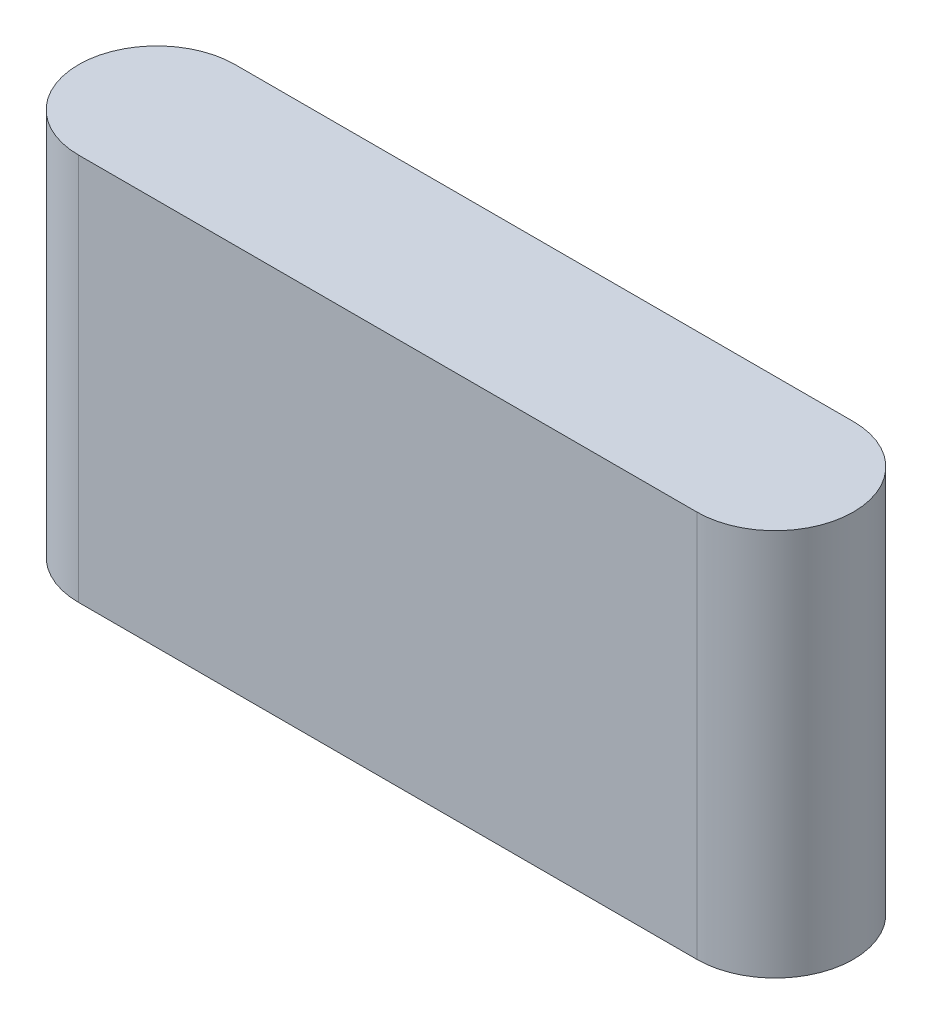
SolidWorks part; units mm, degrees
ref_plane "Přední rovina" through (0, 0, 0) normal (0, 0, 1) x (1, 0, 0)
ref_plane "Horní rovina" through (0, 0, 0) normal (0, 1, 0) x (1, 0, 0)
ref_plane "Pravá rovina" through (0, 0, 0) normal (1, 0, 0) x (0, 0, -1)
sketch "Skica1" plane through (0, 0, 0) normal (0, 0, 1) x (1, 0, 0)
  line L1 (0, 0) -> (-94, 0)
  line L2 (0, 0) -> (0, 47)
  line L3 (0, 47) -> (-94, 47)
  line L4 (-94, 0) -> (-94, 47)
  dimension "D1" = 94
  dimension "D2" = 47
extrude "Přidat vysunutím1" add sketch "Skica1" along normal blind 19
fillet "Zaoblit4" 2 edges at (0, 23.5, 19) (0, 23.5, 0) type full round first side face at (-47, 23.5, 19) second side face at (-47, 23.5, 0) middle face at (0, 23.5, 9.5)
fillet "Zaoblit5" 2 edges at (-94, 23.5, 0) (-94, 23.5, 19) type full round first side face at (-51.75, 23.5, 0) second side face at (-51.75, 23.5, 19) middle face at (-94, 23.5, 9.5)
sketch "Skica2" plane through (0, 0, 0) normal (0, 0, -1) x (-1, 0, 0)
  text T0 "Nano-tex  5.0\r\n5000 mAh" font "Century Gothic" height 3.5
  point P1 (12.777, 12.334)
  point P2 (19.9309, 29.2522)
extrude "Odebrat vysunutím1" cut sketch "Skica2" against normal blind 10
